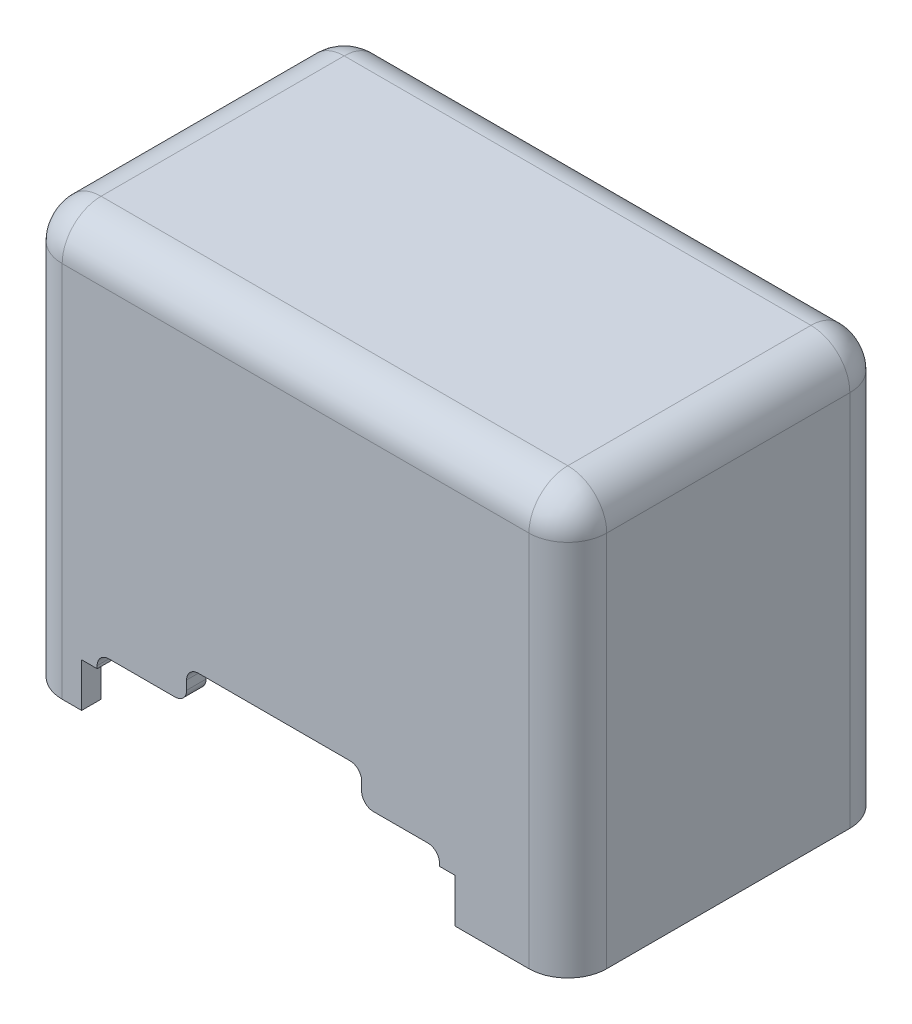
SolidWorks part; units mm, degrees
ref_plane "Front Plane" through (0, 0, 0) normal (0, 0, 1) x (1, 0, 0)
ref_plane "Top Plane" through (0, 0, 0) normal (0, 1, 0) x (1, 0, 0)
ref_plane "Right Plane" through (0, 0, 0) normal (1, 0, 0) x (0, 0, -1)
sketch "Sketch1" plane through (0, 0, 0) normal (0, 1, 0) x (1, 0, 0)
  line L0 (0, 49) -> (0, -33.4057) construction
  line L1 (-48, 49) -> (48, 49)
  line L2 (-48, 49) -> (-48, -33.4057)
  line L3 (-48, -33.4057) -> (48, -33.4057)
  line L4 (48, 49) -> (48, -33.4057)
  line L5 (72, -16.5) -> (28, -16.5)
  line L6 (-58, 49) -> (72, 49)
  line L7 (-58, 49) -> (-58, -23.5)
  line L8 (-58, -23.5) -> (72, -23.5)
  line L9 (72, 49) -> (72, -23.5)
  line L10 (-63, 54) -> (77, 54)
  line L11 (-63, 54) -> (-63, -28.5)
  line L12 (-63, -28.5) -> (77, -28.5)
  line L13 (77, 54) -> (77, -28.5)
  line L14 (-58, 49) -> (72, 49)
  line L15 (-58, 49) -> (-58, 42)
  line L16 (-58, 42) -> (72, 42)
  line L17 (72, 49) -> (72, 42)
  line L18 (-58, -23.5) -> (-28, -23.5)
  line L19 (-58, -23.5) -> (-58, -16.5)
  line L20 (-58, -16.5) -> (-28, -16.5)
  line L21 (-28, -23.5) -> (-28, -16.5)
  line L22 (28, -23.5) -> (28, -16.5)
  line L23 (72, -23.5) -> (28, -23.5)
  line L24 (72, -23.5) -> (72, -16.5)
  circle A0 centre (0, 0) radius 28.5
  dimension "D2" = 57
  dimension "D3" = 77.5
  dimension "D1" = 96
  dimension "D4" = 130
  dimension "D5" = 5
  dimension "D6" = 5
  dimension "D7" = 5
  dimension "D8" = 5
  dimension "D9" = 30
  dimension "D10" = 7
  dimension "D11" = 7
  dimension "D12" = 10
  dimension "D13" = 5
extrude "Boss-Extrude1" add sketch "Sketch1" along normal blind 102 contours L13 L10 L11 L12 L2 L8 L7 L6 L1 L9 L4 | A0 L8 L2 L12 | L0 L8 A0 | L8 L0 A0 | A0 L12 L4 L8 region at (-24, 0, -50.625) region at (6.1243, 0, 25.5158) region at (-6.1243, 0, 25.5158) region at (-29.2854, 0, 26.1432) region at (29.2854, 0, 26.1432)
extrude "Boss-Extrude2" add sketch "Sketch1<3>" along normal blind 5 from surface contours L12 L13 L10 L11 starting at face at (7, 102, -12.75)
sketch "Sketch1<3>" plane through (0, 0, 0) normal (0, 1, 0) x (1, 0, 0) same geometry as "Sketch1"
extrude "Boss-Extrude4" add sketch "Sketch1<4>" along normal blind 11.3 separate body contours L1 L4 L3 L2
sketch "Sketch1<4>" plane through (0, 0, 0) normal (0, 1, 0) x (1, 0, 0) same geometry as "Sketch1"
sketch "Sketch2" plane through (0, 0, 28.5) normal (0, 0, 1) x (1, 0, 0)
  line L0 (0, 11.3) -> (0, 40.9837) construction
  line L1 (-63, 0) -> (77, 0) construction
  line L2 (-48, 11.3) -> (48, 11.3) construction
  line L3 (-44, 0) -> (44, 0)
  line L4 (-44, 0) -> (-44, 15)
  line L5 (-44, 15) -> (44, 15)
  line L6 (44, 0) -> (44, 15)
  dimension "D1" = 88
  dimension "D2" = 15
extrude "Extrude-Thin3" add sketch "Sketch1<5>" along normal blind 15 thin contours L6 thin type one direction wall 10
sketch "Sketch1<5>" plane through (0, 0, 0) normal (0, 1, 0) x (1, 0, 0) same geometry as "Sketch1"
combine bodies "Combine1" operation type subtract main body 105 bodies to subtract 103
extrude "Cut-Extrude2" cut sketch "Sketch2" against normal up to next contours L5 L6 L3 L4
fillet "Fillet1" radius 10 16 edges at (-58, 102, -12.75) (7, 102, 23.5) (72, 102, -12.75) (7, 102, -49) (7, 107, 28.5) (-63, 107, -12.75) (7, 107, -54) (77, 107, -12.75) (-58, 58.5, -49) (72, 58.5, -49) (72, 51, 23.5) (-58, 51, 23.5) (-63, 53.5, 28.5) (-63, 53.5, -54) (77, 53.5, -54) (77, 53.5, 28.5)
fillet "Fillet2" radius 10 3 edges at (-55.0711, 15, -46.0711) (69.0711, 15, -46.0711) (7, 15, -49)
sketch "Sketch3" plane through (-63, 0, 0) normal (-1, 0, 0) x (0, 0, 1)
  line L0 (-54, 0) -> (28.5, 0) construction
  line L1 (-27.75, 0) -> (18.5, 0)
  line L2 (-27.75, 0) -> (-27.75, 75)
  line L3 (-27.75, 75) -> (18.5, 75)
  line L4 (18.5, 0) -> (18.5, 75)
  line L5 (-12.75, 97) -> (-12.75, 0) construction
  line L6 (18.5, 97) -> (-44, 97) construction
  line L7 (28.5, 97) -> (28.5, 0) construction
  dimension "D1" = 75
  dimension "D2" = 15
  dimension "D3" = 10
extrude "Cut-Extrude3" cut sketch "Sketch3" against normal up to next
fillet "Fillet3" radius 10 2 edges at (-59.8301, 75, 18.5) (-60.5, 75, -27.75)
sketch "Sketch4" plane through (0, 0, 28.5) normal (0, 0, 1) x (1, 0, 0)
  line L1 (-21, 11.3) -> (24, 11.3)
  line L2 (-21, 11.3) -> (-21, 23.3)
  line L3 (-21, 23.3) -> (24, 23.3)
  line L4 (24, 11.3) -> (24, 23.3)
  line L5 (-63, 0) -> (-63, 65) construction
  line L6 (44, 11.3) -> (48, 11.3) construction
  dimension "D1" = 12
  dimension "D2" = 42
  dimension "D3" = 45
extrude "Cut-Extrude4" cut sketch "Sketch4" against normal up to next
fillet "Fillet4" radius 3 6 edges at (-44, 15, 26) (-21, 23.3, 26) (24, 23.3, 26) (44, 15, 26) (24, 15, 26) (-21, 15, 26)
